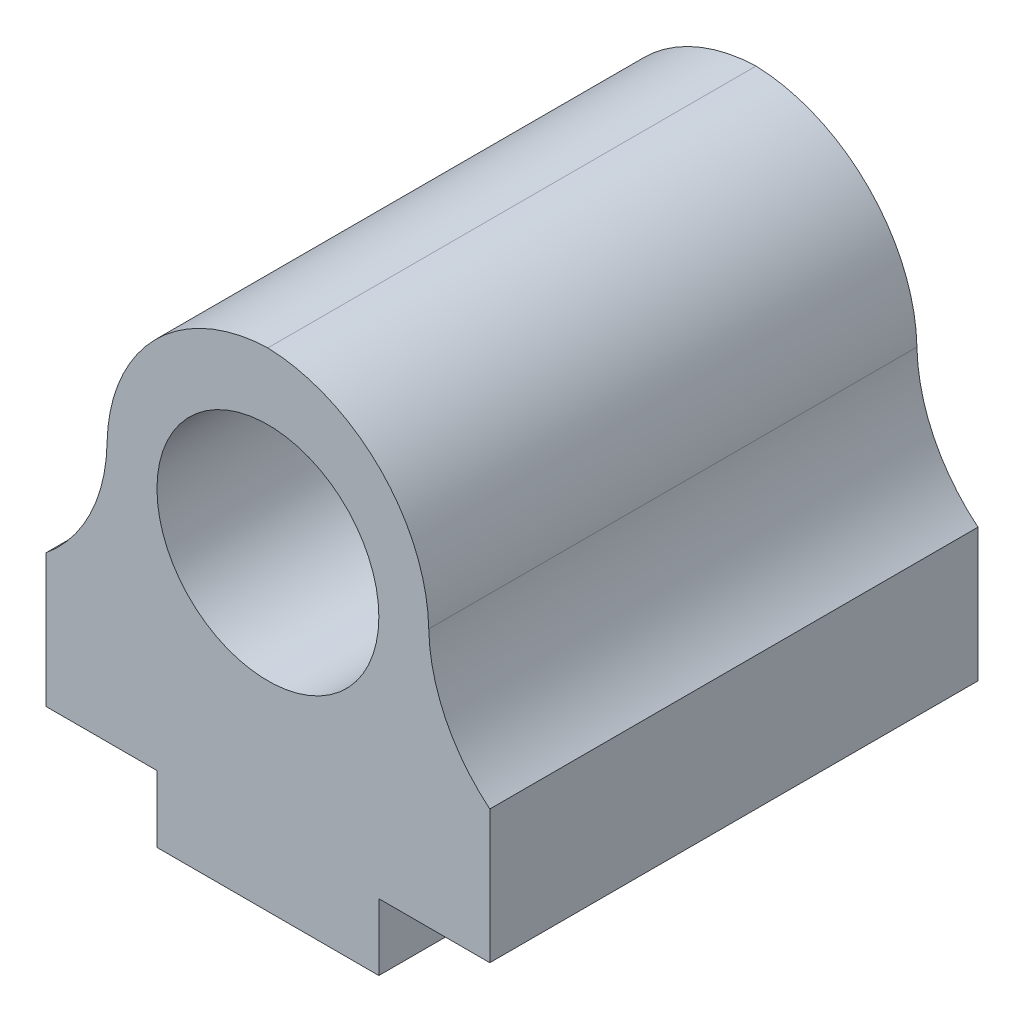
SolidWorks part; units mm, degrees
ref_plane "Front Plane" through (0, 0, 0) normal (0, 0, 1) x (1, 0, 0)
ref_plane "Top Plane" through (0, 0, 0) normal (0, 1, 0) x (1, 0, 0)
ref_plane "Right Plane" through (0, 0, 0) normal (1, 0, 0) x (0, 0, -1)
sketch "Sketch6" plane through (0, 0, 0) normal (0, 1, 0) x (1, 0, 0)
  line L1 (0, 0) -> (20, 0)
  line L2 (0, 0) -> (0, 22)
  line L3 (0, 22) -> (20, 22)
  line L4 (20, 0) -> (20, 22)
  dimension "D1" = 20
  dimension "D2" = 22
extrude "Boss-Extrude5" add sketch "Sketch6" along normal blind 6
sketch "Sketch7" plane through (0, 0, 0) normal (0, -1, 0) x (1, 0, 0)
  line L0 (0, 0) -> (20, 0) construction
  line L1 (5, 0) -> (15, 0)
  line L2 (5, 0) -> (5, -22)
  line L3 (5, -22) -> (15, -22)
  line L4 (15, 0) -> (15, -22)
  line L5 (20, -22) -> (0, -22) construction
  line L6 (0, -22) -> (0, 0) construction
  dimension "D1" = 10
  dimension "D2" = 5
extrude "Boss-Extrude6" add sketch "Sketch7" along normal blind 3
sketch "Sketch8" plane through (0, 6, 0) normal (0, 1, 0) x (1, 0, 0)
  line L0 (20, 22) -> (0, 22) construction
  line L1 (0, 0) -> (20, 0) construction
  line L2 (2.75, 22) -> (17.25, 22)
  line L3 (2.75, 22) -> (2.75, 0)
  line L4 (2.75, 0) -> (17.25, 0)
  line L5 (17.25, 22) -> (17.25, 0)
  line L6 (0, 22) -> (0, 0) construction
  dimension "D1" = 14.5
  dimension "D2" = 2.75
extrude "Boss-Extrude7" add sketch "Sketch8" along normal blind 13
sketch "Sketch9" plane through (0, 0, 0) normal (0, 0, 1) x (1, 0, 0)
  line L0 (2.75, 19) -> (2.75, 6) construction
  line L1 (2.75, 19) -> (17.25, 19) construction
  circle A0 centre (10, 11) radius 5
  dimension "D1" = 7.25
  dimension "D2" = 8
extrude "Cut-Extrude1" cut sketch "Sketch9" against normal through all
fillet "Fillet1" radius 7.5 2 edges at (17.25, 19, -11) (2.75, 19, -11)
fillet "Fillet2" radius 7.5 2 edges at (17.25, 6, -11) (2.75, 6, -11)
